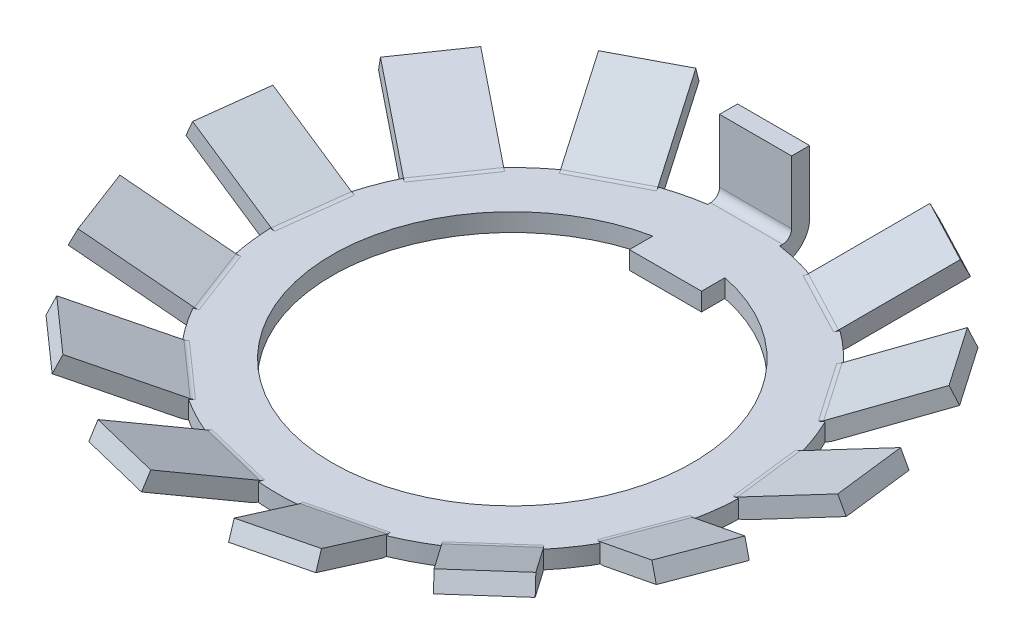
SolidWorks part; units mm, degrees
note: '?' marks a value the reader was unsure of.
revolve "Base" add sketch "Esquisse1" angle 360 about L10
sketch "Esquisse1" plane through (0, 0, 0) normal (0, 0, 1) x (1, 0, 0)
  line L0 (0, -0.0105) -> (0, -4.0105) construction
  line L1 (10, 0) -> (13, 0)
  line L2 (10, 0) -> (10, 1)
  line L3 (10, 1) -> (13, 1)
  line L4 (13, 0) -> (13, 1)
  line L5 (10, 0) -> (-10, 0) construction
  line L6 (13, 0) -> (-13, 0) construction
  line L7 (28.1031, 0) -> (0, 0) construction
  line L8 (0, 0) -> (-36, 0) construction
  line L9 (0, 0) -> (-37.363, 0) construction
  line L10 (0, 0) -> (0, 4) construction
  dimension "Sr4" = 13
  dimension "Epaisseur" = 1
  dimension "Diamètre nominal" = 20
  dimension "Diamètre d4" = 26
  dimension "Diamètre Extérieur d5" = 36
  dimension "Largeur lame ext f" = 4
  dimension "Largeur lame int f1" = 4
  dimension "Sr3" = 10
extrude "Languette pliée" add sketch "Esquisse3" along normal mid plane 4 thin thin type mid plane wall 1
sketch "Esquisse3" plane through (0, 0, 0) normal (1, 0, 0) x (0, 0, -1)
  line L0 (10, 0.5) -> (8.5, 0.5)
  line L2 (0, 0) -> (37, 0) construction
  line L4 (10, 0.5) -> (13, 0.5)
  line L6 (14, 1.5) -> (14, 5)
  line L13 (-10, 1) -> (-10, 0) construction
  line L14 (13, 1) -> (-13, 1) construction
  line L15 (10, 0) -> (10, 1) construction
  line L16 (13, 0) -> (13, 1) construction
  arc A0 (13, 0.5) -> (14, 1.5) centre (13, 1.5) ccw
  dimension "Rl2" = 1
  dimension "LLC" = 4
  dimension "Longueur M" = 18.5
ref_plane "Face" through (0, 0, 0) normal (0, 0, 1) x (1, 0, 0)
ref_plane "Dessus" through (0, 0, 0) normal (0, 1, 0) x (1, 0, 0)
ref_plane "Droite" through (0, 0, 0) normal (1, 0, 0) x (0, 0, -1)
ref_axis "Axe1" through (0, 5.25, 0) along (0, -1, 0)?
ref_plane "Plan Languette" through (0, 0, 0) normal (-0.8855, 0, -0.4647) x (-0.4647, 0, 0.8855)
sketch "Esquisse2" plane through (0, 0, 0) normal (-0.8855, 0, -0.4647) x (-0.4647, 0, 0.8855)
  line L0 (-10, 0.5) -> (-12.5774, 0.5)
  line L3 (-13, 0.5937) -> (-18, 2.9252)
  line L4 (0, 0) -> (0, 4) construction
  line L5 (-10, 1) -> (-10, 0) construction
  line L6 (-13, 1) -> (-13, 0) construction
  arc A0 (-12.5774, 0.5) -> (-13, 0.5937) centre (-12.5774, 1.5) cw
  point P9 (-12.7991, 0.5)
  dimension "D1" = 25
  dimension "Sd5" = 18
extrude "Languette" add sketch "Esquisse2" along normal mid plane 4 thin thin type mid plane wall 1
pattern_circular "Nbr de languettes" count 12 every 27.692 about axis through (0, 0, 0) along (0, 1, 0) of "Languette"
equation "\"Sr4@Esquisse1\" = \"Diamètre d4@Esquisse1\"/2"
equation "\"Sr3@Esquisse1\" = \"Diamètre nominal@Esquisse1\"/2"
equation "\"RL2@Esquisse2\" = \"Epaisseur@Esquisse1\""
equation "\"Sd5@Esquisse2\" = \"Diamètre Extérieur d5@Esquisse1\" /2"
equation "\"Rl2@Esquisse3\" = \"Epaisseur@Esquisse1\"  "
equation "\"LLC@Esquisse3\" =  \"Largeur lame ext f@Esquisse1\"  "
equation "\"EpL0@Languette\" =  \"Epaisseur@Esquisse1\"  "
equation "\"Sdf@Languette\" =  \"Largeur lame ext f@Esquisse1\"  "
equation "\"Df1@Languette pliée\" =  \"Largeur lame int f1@Esquisse1\"  "
equation "\"EpL1@Languette pliée\" =  \"Epaisseur@Esquisse1\"  "
equation "\"D1@Nbr de languettes\" =int( (\"Diamètre d4@Esquisse1\"*pi)/(1.5*\"Df1@Languette pliée\"))-1"
equation "\"D1@Plan Languette\" = 180+(360/int( (\"Diamètre d4@Esquisse1\"*pi)/(1.5*\"Df1@Languette pliée\")))"
equation "\"D2@Nbr de languettes\" = \"D1@Plan Languette\"-180"
